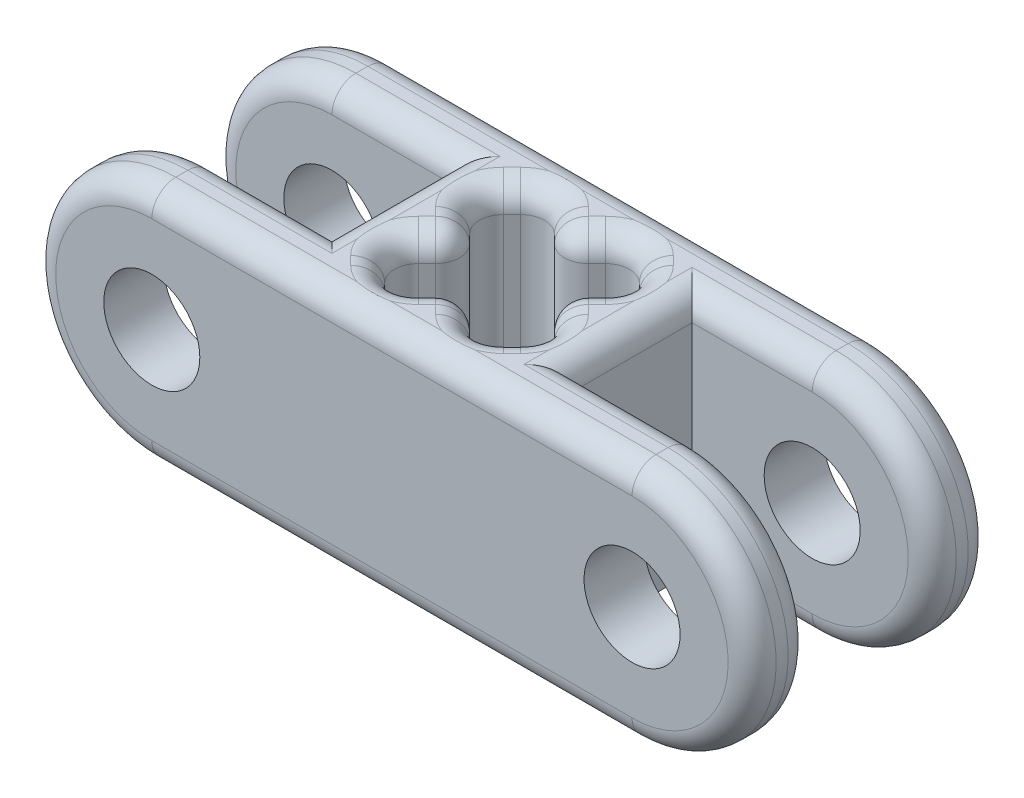
SolidWorks part; units mm, degrees
ref_plane "Plan de face" through (0, 0, 0) normal (0, 0, 1) x (1, 0, 0)
ref_plane "Plan de dessus" through (0, 0, 0) normal (0, 1, 0) x (1, 0, 0)
ref_plane "Plan de droite" through (0, 0, 0) normal (1, 0, 0) x (0, 0, -1)
sketch "Esquisse1" plane through (0, 0, 0) normal (0, 0, 1) x (1, 0, 0)
  line L1 (0, 0) -> (40, 0)
  line L2 (0, 0) -> (0, 20) construction
  line L3 (0, 20) -> (40, 20)
  line L4 (40, 0) -> (40, 20) construction
  arc A0 (0, 0) -> (0, 20) centre (0, 10) cw
  arc A1 (40, 0) -> (40, 20) centre (40, 10) ccw
  circle A2 centre (0, 10) radius 4
  circle A3 centre (40, 10) radius 4
  dimension "D1" = 20
  dimension "D2" = 8
  dimension "D3" = 40
extrude "Boss.-Extru.1" add sketch "Esquisse1" along normal blind 20
sketch "Esquisse2" plane through (0, 20, 0) normal (0, 1, 0) x (1, 0, 0)
  line L0 (-10, 0) -> (-10, -20) construction
  line L1 (-10, -5) -> (10, -5)
  line L2 (-10, -5) -> (-10, -15)
  line L3 (-10, -15) -> (10, -15)
  line L4 (10, -5) -> (10, -15)
  line L5 (50, -5) -> (30, -5)
  line L6 (50, -5) -> (50, -15)
  line L7 (50, -15) -> (30, -15)
  line L8 (30, -5) -> (30, -15)
  line L9 (50, -20) -> (50, 0) construction
  line L10 (0, -20) -> (0, 0) construction
  point P12 (-10, -10)
  point P13 (0, -10)
  dimension "D1" = 20
  dimension "D2" = 10
extrude "Enlèv. mat.-Extru.1" cut sketch "Esquisse2" against normal through all
ref_axis "Axe1" through (40, 10, 20) along (0, 0, -1)
ref_plane "Plan1" through (0, 10, 0) normal (0, 1, 0) x (1, 0, 0)
sketch "Esquisse3" plane through (0, 20, 0) normal (0, 1, 0) x (1, 0, 0)
  line L0 (20, 0) -> (20, -20) construction
  line L1 (40, 0) -> (0, 0) construction
  line L2 (40, -20) -> (0, -20) construction
  line L3 (10, -10) -> (30, -10) construction
  line L4 (10, -15) -> (10, -5) construction
  line L5 (30, -5) -> (30, -15) construction
  line L6 (20, -6.4645) -> (23.5355, -2.9289)
  line L7 (23.5355, -2.9289) -> (27.0711, -6.4645)
  line L8 (27.0711, -6.4645) -> (23.5355, -10)
  line L9 (12.9289, -6.4645) -> (16.4645, -10)
  line L10 (16.4645, -2.9289) -> (12.9289, -6.4645)
  line L11 (20, -6.4645) -> (16.4645, -2.9289)
  line L12 (23.5355, -17.0711) -> (27.0711, -13.5355)
  line L13 (16.4645, -17.0711) -> (12.9289, -13.5355)
  line L14 (20, -13.5355) -> (16.4645, -17.0711)
  line L15 (20, -13.5355) -> (23.5355, -17.0711)
  line L16 (27.0711, -13.5355) -> (23.5355, -10)
  line L17 (12.9289, -13.5355) -> (16.4645, -10)
  dimension "D1" = 5
extrude "Enlèv. mat.-Extru.2" cut sketch "Esquisse3" against normal through all
fillet "Congé1" radius 2 58 edges at (50, 10, 0) (20, 0, 0) (-10, 10, 0) (35, 0, 5) (50, 10, 5) (35, 0, 15) (50, 10, 15) (50, 10, 20) (20, 0, 20) (-10, 10, 20) (5, 0, 15) (-10, 10, 15) (5, 0, 5) (-10, 10, 5) (18.2322, 0, 15.3033) (14.6967, 0, 15.3033) (16.4645, 10, 17.0711) (20, 20, 0) (35, 20, 5) (30, 20, 10) (35, 20, 15) (20, 20, 20) (5, 20, 15) (10, 20, 10) (5, 20, 5) (14.6967, 20, 15.3033) (18.2322, 20, 15.3033) (25.3033, 0, 8.2322) (25.3033, 20, 8.2322) (25.3033, 0, 11.7678) (23.5355, 10, 10) (25.3033, 20, 11.7678) (20, 10, 13.5355) (21.7678, 0, 15.3033) (21.7678, 20, 15.3033) (23.5355, 10, 17.0711) (25.3033, 0, 15.3033) (27.0711, 10, 13.5355) (25.3033, 20, 15.3033) (14.6967, 0, 11.7678) (12.9289, 10, 13.5355) (14.6967, 20, 11.7678) (14.6967, 0, 8.2322) (16.4645, 10, 10) (14.6967, 20, 8.2322) (14.6967, 0, 4.6967) (12.9289, 10, 6.4645) (14.6967, 20, 4.6967) (27.0711, 10, 6.4645) (25.3033, 0, 4.6967) (25.3033, 20, 4.6967) (23.5355, 10, 2.9289) (21.7678, 0, 4.6967) (21.7678, 20, 4.6967) (20, 10, 6.4645) (18.2322, 0, 4.6967) (16.4645, 10, 2.9289) (18.2322, 20, 4.6967)
